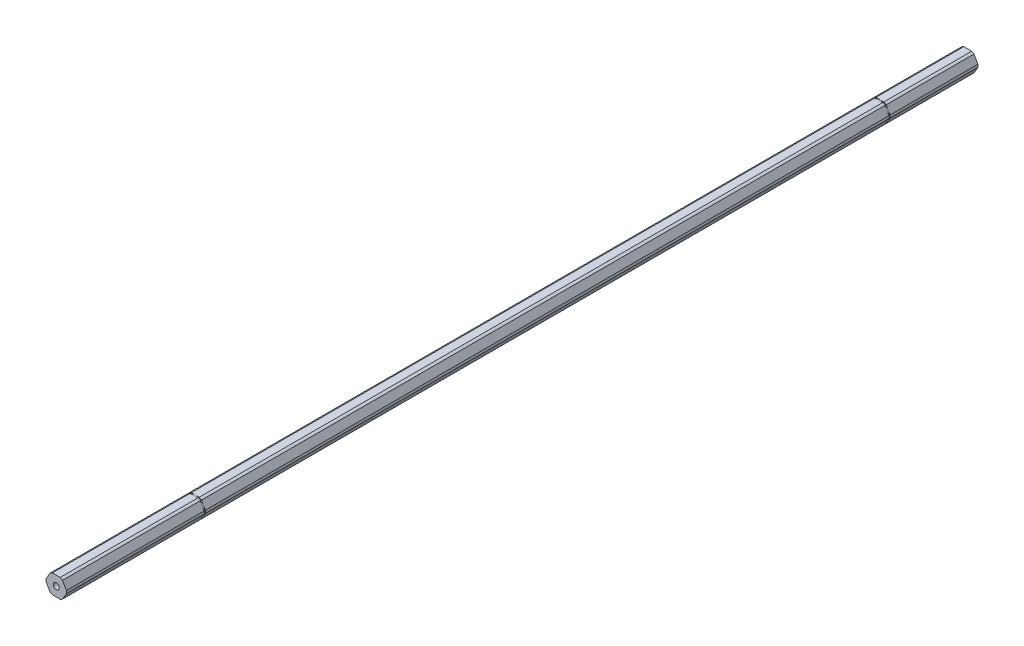
SolidWorks part; units mm, degrees
material "6061-T6 (SS)"
ref_plane "Front Plane" through (0, 0, 0) normal (0, 0, 1) x (1, 0, 0)
ref_plane "Top Plane" through (0, 0, 0) normal (0, 1, 0) x (1, 0, 0)
ref_plane "Right Plane" through (0, 0, 0) normal (1, 0, 0) x (0, 0, -1)
sketch "Sketch1" plane through (0, 0, 0) normal (0, 0, 1) x (1, 0, 0)
  line L1 (3.6662, 6.35) -> (-3.6662, 6.35)
  line L2 (-3.6662, 6.35) -> (-7.3323, 0)
  line L3 (-7.3323, 0) -> (-3.6662, -6.35)
  line L4 (-3.6662, -6.35) -> (3.6662, -6.35)
  line L5 (3.6662, -6.35) -> (7.3323, 0)
  line L6 (7.3323, 0) -> (3.6662, 6.35)
  circle A0 centre (0, 0) radius 6.35 construction
  circle A1 centre (0, 0) radius 6.875
  circle A2 centre (0, 0) radius 2
  point P1 (0, 6.35)
  dimension "D2" = 13.75
  dimension "D3" = 4
  dimension "D1" = 12.7
extrude "Boss-Extrude1" add sketch "Sketch1" along normal blind 609.6 contours L6 A1 L1 L2 L3 L4 L5 A2 region at (3.3439, 5.7918, 0)
sketch "Sketch2" plane through (0, 0, 0) normal (0, 1, 0) x (1, 0, 0)
  line L0 (2.635, -609.6) -> (-2.635, -609.6) construction
  line L1 (-6.35, -516.636) -> (6.35, -516.636)
  line L2 (-6.35, -516.636) -> (-6.35, -517.525)
  line L3 (-6.35, -517.525) -> (6.35, -517.525)
  line L4 (6.35, -516.636) -> (6.35, -517.525)
  line L5 (0, -609.6) -> (0, 0) construction
  line L6 (8.001, -516.636) -> (-8.001, -516.636)
  line L7 (8.001, -516.636) -> (8.001, -517.525)
  line L8 (8.001, -517.525) -> (-8.001, -517.525)
  line L9 (-8.001, -516.636) -> (-8.001, -517.525)
  line L10 (2.635, 0) -> (-2.635, 0) construction
  line L11 (-6.35, -58.7375) -> (6.35, -58.7375)
  line L12 (-6.35, -58.7375) -> (-6.35, -59.6265)
  line L13 (-6.35, -59.6265) -> (6.35, -59.6265)
  line L14 (6.35, -58.7375) -> (6.35, -59.6265)
  line L16 (6.35, -58.7375) -> (8.001, -58.7375)
  line L17 (6.35, -58.7375) -> (6.35, -59.6265)
  line L18 (6.35, -59.6265) -> (8.001, -59.6265)
  line L19 (8.001, -58.7375) -> (8.001, -59.6265)
  point P6 (0, -609.6)
  point P7 (0, -517.525)
  point P21 (0, -58.7375)
  dimension "D1" = 92.075
  dimension "D2" = 0.889
  dimension "D3" = 12.7
  dimension "D4" = 1.651
  dimension "D5" = 1.651
  dimension "D6" = 58.7375
  dimension "D7" = 0.889
  dimension "D8" = 12.7
  dimension "D9" = 1.651
revolve "Cut-Revolve1" cut sketch "Sketch2" angle 360 about L5 region at (7.1755, 0, 517.0805) region at (7.1755, 0, 59.182)
equation "\"D2@Sketch1\"=13.750000mm"
equation "\"D3@Sketch1\"=4mm"
equation "\"D5@Sketch2\"=\"D4@Sketch2\""
